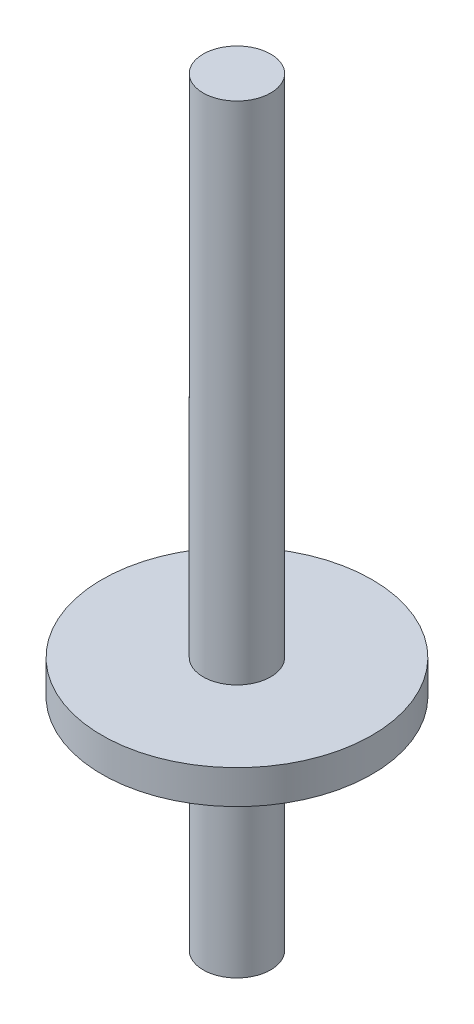
SolidWorks part; units mm, degrees
ref_plane "Front Plane" through (0, 0, 0) normal (0, 0, 1) x (1, 0, 0)
ref_plane "Top Plane" through (0, 0, 0) normal (0, 1, 0) x (1, 0, 0)
ref_plane "Right Plane" through (0, 0, 0) normal (1, 0, 0) x (0, 0, -1)
sketch "Sketch1" plane through (0, 0, 0) normal (0, 1, 0) x (1, 0, 0)
  circle A0 centre (0, 0) radius 10
  dimension "D1" = 20
extrude "Boss-Extrude1" add sketch "Sketch1" along normal blind 149.8283
sketch "Sketch2" plane through (0, 0, 0) normal (0, -1, 0) x (-1, 0, 0)
  circle A0 centre (0, 0) radius 40.0005
extrude "Boss-Extrude2" add sketch "Sketch2" along normal blind 10
extrude "Boss-Extrude3" add sketch "Sketch1<2>" against normal blind 75.187
sketch "Sketch1<2>" plane through (0, 0, 0) normal (0, 1, 0) x (1, 0, 0) same geometry as "Sketch1"
